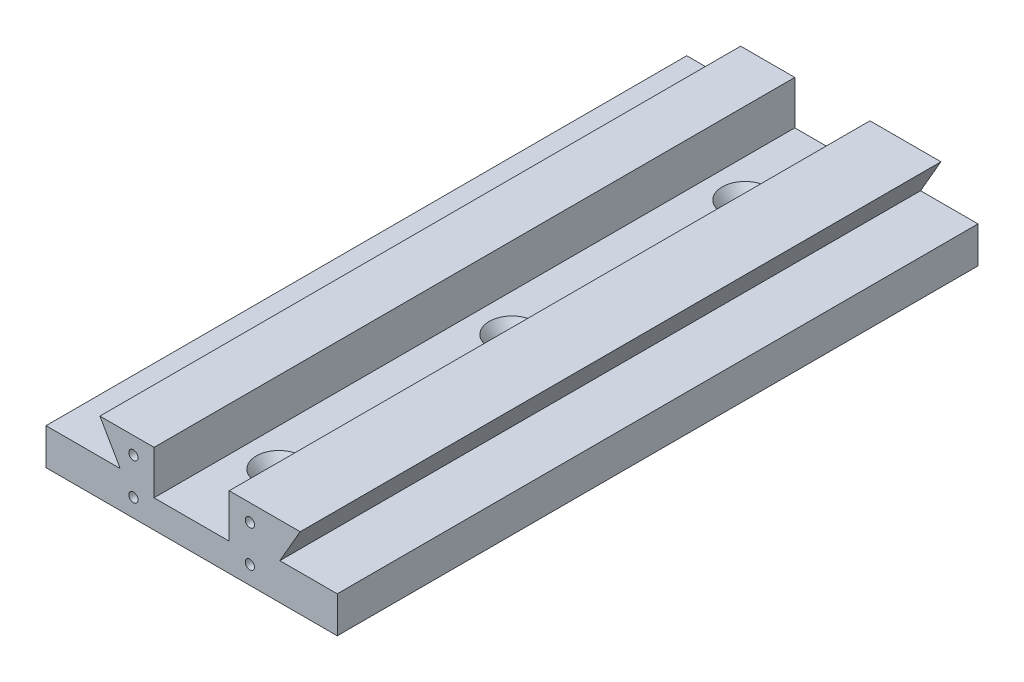
SolidWorks part; units mm, degrees
material "Ductile Iron"
ref_plane "Front Plane" through (0, 0, 0) normal (0, 0, 1) x (1, 0, 0)
ref_plane "Top Plane" through (0, 0, 0) normal (0, 1, 0) x (1, 0, 0)
ref_plane "Right Plane" through (0, 0, 0) normal (1, 0, 0) x (0, 0, -1)
sketch "Sketch6" plane through (0, 0, 0) normal (0, 0, 1) x (1, 0, 0)
  line B0 (-63.5, 0) -> (63.5, 0)
  line B1 (63.5, 0) -> (63.5, 15.875)
  line B2 (63.5, 15.875) -> (38.4596, 15.875)
  line B3 (38.4596, 15.875) -> (47.625, 31.75)
  line B4 (47.625, 31.75) -> (16.0563, 31.75)
  line B5 (-40.2927, 31.75) -> (-31.1272, 15.875)
  line B6 (-31.1272, 15.875) -> (-63.5, 15.875)
  line B7 (-63.5, 15.875) -> (-63.5, 0)
  line B8 (-38.4596, 15.875) -> (-47.625, 31.75)
  line B9 (-47.625, 31.75) -> (-40.2927, 31.75)
  line B10 (-16.0563, 31.75) -> (-16.0563, 12.7) construction
  line B11 (-16.0563, 12.7) -> (16.0563, 12.7) construction
  line B12 (16.0563, 12.7) -> (16.0563, 31.75) construction
  line B13 (-16.0563, 31.75) -> (-40.2927, 31.75)
  line B14 (-63.5, 15.875) -> (-63.5, 47.625)
  line B15 (-63.5, 47.625) -> (63.5, 47.625)
  line B16 (63.5, 47.625) -> (63.5, 15.875)
  line B17 (-16.0563, 31.75) -> (16.0563, 31.75) construction
  line B18 (0, 47.625) -> (0, 0) construction
  line B19 (-38.4596, 15.875) -> (38.4596, 15.875) construction
  line B20 (-28.702, 36.957) -> (28.702, 36.957) construction
  line B21 (-25.4, 7.874) -> (25.4, 7.874) construction
  line B22 (-25.4, 7.874) -> (-25.4, 23.8125) construction
  line B23 (25.4, 7.874) -> (25.4, 23.8125) construction
  line B24 (-52.832, 23.8125) -> (52.832, 23.8125) construction
  circle B25 centre (0, 22.225) radius 18.669 construction
  line B26 (40.2927, 31.75) -> (31.1272, 15.875)
  line B27 (31.1272, 15.875) -> (38.4596, 15.875)
  line B28 (-15.875, 31.75) -> (-15.875, 12.7)
  line B29 (-16.0563, 31.75) -> (-15.875, 31.75)
  line B30 (-15.875, 12.7) -> (15.875, 12.7)
  line B31 (15.875, 12.7) -> (15.875, 31.75)
  line B32 (15.875, 31.75) -> (16.0563, 31.75)
sketch_block_instance "dovetail pair-2"
sketch_block "dovetail pair" parameters "D8"=37.338, "D1"=60, "D2"=127, "D3"=6.35, "D4"=15.875, "D5"=31.75, "D6"=95.25, "D7"=19.05, "D9"=60, "D10"=31.75, "D11"=50.8, "D12"=23.876, "D13"=7.874, "D14"=10.668, "D15"=34.798, "D16"=21.082, "D17"=7.9375, "D18"=24.4437
sketch "dovetail-male-profile" plane through (0, 0, 0) normal (0, 0, 1) x (1, 0, 0)
  line L0 (47.3317, 31.242) -> (16.383, 31.242)
  line L1 (-16.383, 31.242) -> (-39.9994, 31.242)
  line L2 (16.383, 31.242) -> (16.383, 12.192)
  line L3 (16.383, 12.192) -> (-16.383, 12.192)
  line L4 (-16.383, 12.192) -> (-16.383, 31.242)
  line L5 (0, 47.625) -> (0, 0) construction
  line L7 (63.5, 15.875) -> (38.4596, 15.875) construction
  line L8 (63.5, 0) -> (63.5, 15.875) construction
  line L9 (-63.5, 0) -> (63.5, 0) construction
  line L10 (-63.5, 15.875) -> (-63.5, 0) construction
  line L11 (-31.1272, 15.875) -> (-63.5, 15.875) construction
  line L12 (38.4596, 15.875) -> (47.625, 31.75) construction
  line L13 (-31.1272, 15.875) -> (-39.9994, 31.242)
  line L15 (63.5, 15.875) -> (38.4596, 15.875)
  line L16 (63.5, 0) -> (63.5, 15.875)
  line L17 (-63.5, 0) -> (63.5, 0)
  line L18 (-63.5, 15.875) -> (-63.5, 0)
  line L19 (-31.1272, 15.875) -> (-63.5, 15.875)
  line L20 (-40.2927, 31.75) -> (-31.1272, 15.875) construction
  line L21 (38.4596, 15.875) -> (47.3317, 31.242)
  line L23 (47.625, 31.75) -> (16.0563, 31.75) construction
  line L25 (-16.0563, 12.7) -> (16.0563, 12.7) construction
  line L27 (15.875, 12.7) -> (15.875, 31.75) construction
  point P23 (0, 12.192)
  dimension "D2" = 0.508
  dimension "D1" = 0.508
  dimension "D3" = 0.508
extrude "x-guide-extrude" add sketch "dovetail-male-profile" along normal blind 279.4 contours L21 L0 L2 L3 L4 L1 L13 L19 L18 L17 L16 L15 region at (1.7017, 12.0113, 0)
hole_wizard "end plate holes" positions "Sketch2" profile "Sketch3" tap size "#10-32" standard "ANSI Inch"
sketch "Sketch2" plane through (0, 0, 0) normal (0, 0, -1) x (-1, 0, 0)
  point P27 (-25.4, 23.8125)
  point P29 (25.4, 23.8125)
  point P31 (25.4, 7.874)
  point P33 (-25.4, 7.874)
sketch "Sketch3" plane through (25.4, 23.8125, 0) normal (1, 0, 0) x (0, 1, 0)
  line L0 (0, 0) -> (0, 13.1513)
  line L1 (0, 13.1513) -> (2.0193, 11.938)
  line L2 (2.0193, 11.938) -> (2.0193, 0)
  line L3 (2.0193, 0) -> (0, 0)
  line L4 (0, 13.1513) -> (-2.0193, 11.938) construction
  line L5 (0, -6.35) -> (0, 107.95) construction
  dimension "Tap Drill Dia." = 4.0386
  dimension "Tap Drill Depth" = 11.938
  dimension "Drill Angle" = 118
cosmetic thread "Hole Thread1" parameters "D1"=9.652, "D2"=4.826
cosmetic thread "Hole Thread2" parameters "D1"=9.652, "D2"=4.826
cosmetic thread "Hole Thread9" parameters "D1"=9.652, "D2"=4.826
cosmetic thread "Hole Thread10" parameters "D1"=9.652, "D2"=4.826
hole_wizard "end plate holes 2" positions "Sketch4" profile "Sketch5" tap size "#10-32" standard "ANSI Inch"
sketch "Sketch4" plane through (0, 0, 279.4) normal (0, 0, 1) x (1, 0, 0)
  point P8 (25.4, 23.8125)
  point P10 (25.4, 7.874)
  point P12 (-25.4, 7.874)
  point P14 (-25.4, 23.8125)
cosmetic thread "Hole Thread5" parameters "D1"=9.652, "D2"=4.826
cosmetic thread "Hole Thread6" parameters "D1"=9.652, "D2"=4.826
cosmetic thread "Hole Thread11" parameters "D1"=9.652, "D2"=4.826
cosmetic thread "Hole Thread12" parameters "D1"=9.652, "D2"=4.826
sketch "Sketch5" plane through (25.4, 23.8125, 279.4) normal (1, 0, 0) x (0, -1, 0)
  line L0 (0, 0) -> (0, 13.1513)
  line L1 (0, 13.1513) -> (2.0193, 11.938)
  line L2 (2.0193, 11.938) -> (2.0193, 0)
  line L5 (2.0193, 0) -> (0, 0)
  line L10 (0, 13.1513) -> (-2.0193, 11.938) construction
  line L11 (0, -6.35) -> (0, 107.95) construction
  dimension "Tap Drill Dia." = 4.0386
  dimension "Tap Drill Depth" = 11.938
  dimension "Drill Angle" = 118
hole_wizard "bed mount CSK for 3/8 Flat Head Socket Cap Screw1" positions "Sketch8" profile "Sketch7" countersink size "3/8" standard "ANSI Inch" end condition up to next
sketch "Sketch8" plane through (0, 12.192, 0) normal (0, 1, 0) x (1, 0, 0)
  line L0 (-63.5, -139.7) -> (63.5, -139.7) construction
  line L1 (-63.5, -279.4) -> (-63.5, 0) construction
  line L2 (63.5, -279.4) -> (63.5, 0) construction
  line L3 (0, -38.1) -> (0, -241.3) construction
  point P0 (0, -38.1)
  point P2 (0, -139.7)
  point P4 (0, -241.3)
  dimension "D1" = 101.6
sketch "Sketch7" plane through (0, 12.192, 38.1) normal (1, 0, 0) x (0, 0, 1)
  line L0 (0, 0) -> (0, 12.192)
  line L1 (0, 12.192) -> (5.0419, 12.192)
  line L2 (5.0419, 12.192) -> (5.0419, 5.6101)
  line L3 (5.0419, 5.6101) -> (9.9187, 0)
  line L5 (9.9187, 0) -> (0, 0)
  line L6 (-5.0419, 5.6101) -> (-9.9187, 0) construction
  line L11 (0, -6.35) -> (0, 107.95) construction
  dimension "Thru Hole Dia." = 10.0838
  dimension "Thru Hole Depth" = 12.192
  dimension "Near C'Sink Dia." = 19.8374
  dimension "Near C'Sink Angle" = 82
equation "\"dovetail-angle\" = 60"
equation "\"dovetail-stock-width\" = 5"
equation "\"dovetail-stock-height\" = 1.25"
equation "\"dovetail-throat-width\" = \"dovetail-stock-width\" - (2 * \"dovetail-depth\")"
equation "\"dovetail-depth\" = 0.5 * \"dovetail-stock-height\""
equation "\"delta-x\" = 6"
equation "\"delta-y\" = 3"
equation "\"gib-thickness\" = 0.25"
equation "\"x-slide-length\" = \"dovetail-stock-width\" + \"delta-x\""
equation "\"y-slide-length\" = \"dovetail-stock-width\" + \"delta-y\""
equation "\"D1@x-guide-extrude\"=\"x-slide-length\""
equation "\"dog-point-diam\" = .149"
equation "\"dog-point-length\" = .067"
equation "\"dovetail-double-height\" = 2 * \"dovetail-depth\" + 0.5"
equation "\"acme-major-diam\" = .5"
equation "\"acme-pitch-diam\" = 0.45"
equation "\"acme-minor-diam\" = 0.4"
equation "\"acme-nut-od\" = 1.47"
equation "\"acme-nut-length\" = 1"
equation "\"acme-nut-trim-height\" = .75"
equation "\"screw-bearing-od\" = 0.5"
equation "\"screw-bearing-length\" = .375"
equation "\"end-plate-thickness\" = \"screw-bearing-length\""
equation "\"screw-bearing-id\" = .3125"
equation "\"screw-add-length\" = 2 * \"end-plate-thickness\" + 1 + 0.5"
equation "\"acme-nut-mount-hole-space-horz\" = 0.95"
equation "\"acme-nut-mount-hole-space-vert\" = 0.5 * \"acme-nut-length\""
equation "\"x-screw-length\" = \"x-slide-length\" + \"screw-add-length\""
equation "\"y-screw-length\" = \"y-slide-length\" + \"screw-add-length\""
equation "\"D2@dovetail pair\"=\"dovetail-stock-width\""
equation "\"D1@dovetail pair\"=\"dovetail-angle\""
equation "\"D3@dovetail pair\"=\"gib-thickness\""
equation "\"D4@dovetail pair\"=\"dovetail-depth\""
equation "\"D5@dovetail pair\"=\"dovetail-stock-height\""
equation "\"D6@dovetail pair\"=\"dovetail-throat-width\""
equation "\"D10@dovetail pair\"=\"dovetail-stock-height\""
equation "\"D7@dovetail pair\"=\"acme-nut-trim-height\""
equation "\"D8@dovetail pair\"=\"acme-nut-od\""
equation "\"D9@dovetail pair\"=\"dovetail-angle\""
equation "\"D17@dovetail pair\"=\"dovetail-depth\"/2"
equation "\"acme-nut-trim-width\" = 1.25"
equation "\"vise-hole-center-dist\" = 6.75"
equation "\"wiper_plate_clearance\" = .03"
equation "\"dial-width\" = 0.5"
equation "\"quarter-twenty-free-fit\" = .2667"
equation "\"acme_nut_clearance\" = .02"
equation "\"dovetail_male_clearance\" = .02"
equation "\"D1@dovetail-male-profile\"=\"dovetail_male_clearance\""
equation "\"D2@dovetail-male-profile\"=\"dovetail_male_clearance\""
equation "\"D3@dovetail-male-profile\"=\"dovetail_male_clearance\""
